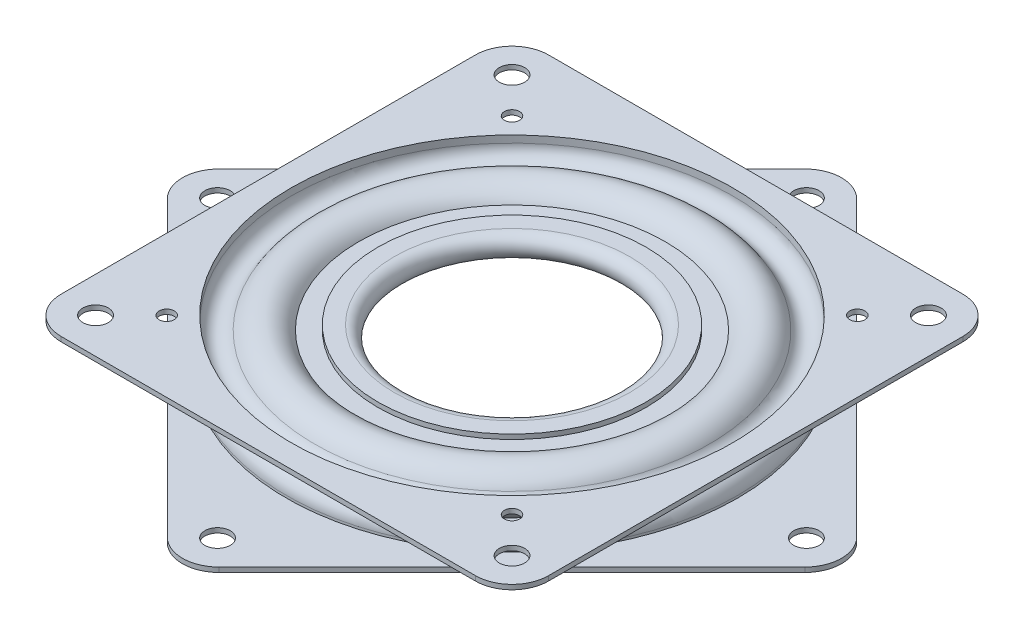
SolidWorks part; units mm, degrees
note: The reader was unsure of these and kept them because the rebuilt part matched: shared geometry of "Sketch3<3>".
material "Plain Carbon Steel"
ref_plane "Front Plane" through (0, 0, 0) normal (0, 0, 1) x (1, 0, 0)
ref_plane "Top Plane" through (0, 0, 0) normal (0, 1, 0) x (1, 0, 0)
ref_plane "Right Plane" through (0, 0, 0) normal (1, 0, 0) x (0, 0, -1)
sketch "Sketch1" plane through (0, 0, 0) normal (0, 1, 0) x (1, 0, 0)
  line L0 (0, -53.8815) -> (-53.8815, 0) construction
  line L1 (-38.1, 38.1) -> (38.1, 38.1) construction
  line L2 (-38.1, 38.1) -> (-38.1, -38.1) construction
  line L3 (-38.1, -38.1) -> (38.1, -38.1) construction
  line L4 (38.1, 38.1) -> (38.1, -38.1) construction
  line L5 (0, -38.1) -> (0, 38.1) construction
  line L6 (-38.1, 0) -> (38.1, 0) construction
  line L7 (0, -53.8815) -> (53.8815, 0) construction
  line L8 (-53.8815, 0) -> (0, 53.8815) construction
  line L9 (53.8815, 0) -> (0, 53.8815) construction
  line L10 (0, -53.8815) -> (0, 53.8815) construction
  line L11 (-53.8815, 0) -> (53.8815, 0) construction
  line L12 (38.1, -38.1) -> (-38.1, 38.1) construction
  line L13 (38.1, 38.1) -> (-38.1, -38.1) construction
  line L15 (-26.9875, 26.9875) -> (26.9875, 26.9875) construction
  line L16 (-26.9875, 26.9875) -> (-26.9875, -26.9875) construction
  line L17 (-26.9875, -26.9875) -> (26.9875, -26.9875) construction
  line L18 (26.9875, 26.9875) -> (26.9875, -26.9875) construction
  line L19 (-32.5437, 32.5437) -> (32.5437, 32.5437) construction
  line L20 (-32.5437, 32.5437) -> (-32.5437, -32.5437) construction
  line L21 (-32.5437, -32.5437) -> (32.5437, -32.5437) construction
  line L22 (32.5437, 32.5437) -> (32.5437, -32.5437) construction
  circle A0 centre (0, 0) radius 16.637 construction
  circle A1 centre (32.5437, -32.5437) radius 1.9844 construction
  circle A2 centre (-32.5437, -32.5437) radius 1.9844 construction
  circle A3 centre (-32.5437, 32.5437) radius 1.9844 construction
  circle A4 centre (32.5437, 32.5437) radius 1.9844 construction
  circle A5 centre (26.9875, 26.9875) radius 1.1906 construction
  circle A6 centre (-26.9875, 26.9875) radius 1.1906 construction
  circle A7 centre (-26.9875, -26.9875) radius 1.1906 construction
  circle A8 centre (26.9875, -26.9875) radius 1.1906 construction
  dimension "ID" = 33.274
  dimension "Inner Mounting Hole Dia." = 2.3813
  dimension "Outer Mounting Hole Dia." = 3.9688
  dimension "Length" = 76.2
  dimension "Width" = 76.2
  dimension "Inner Mounting Length" = 53.975
  dimension "Outer Mounting Length" = 65.0875
sketch "Sketch2" plane through (0, 0, 0) normal (0, 0, 1) x (1, 0, 0)
  line L0 (0, 3.937) -> (0, -3.937) construction
  line L1 (-38.1, 3.937) -> (38.1, 3.937) construction
  line L2 (-38.1, 3.937) -> (-38.1, -3.937) construction
  line L3 (-38.1, -3.937) -> (38.1, -3.937) construction
  line L4 (38.1, 3.937) -> (38.1, -3.937) construction
  line L5 (-38.1, 0) -> (38.1, 0) construction
  line L6 (-38.1, 3.2004) -> (38.1, 3.2004) construction
  line L7 (-38.1, -3.2004) -> (38.1, -3.2004) construction
  point P8 (0, 0)
  dimension "Overall Height" = 7.874
  dimension "Plate Thickness" = 0.7366
sketch "Sketch3" plane through (0, 0, 0) normal (0, 0, 1) x (1, 0, 0)
  line L0 (38.1, 3.937) -> (34.5177, 3.937)
  line L1 (-38.1, 3.937) -> (38.1, 3.937) construction
  line L2 (34.5177, 3.937) -> (34.5177, 2.8346)
  line L3 (23.943, 1.9406) -> (18.4086, 1.9406)
  line L4 (38.1, -3.937) -> (34.5177, -3.937)
  line L5 (-38.1, -3.937) -> (38.1, -3.937) construction
  line L6 (34.5177, -3.937) -> (34.5177, -2.8346)
  line L7 (34.5177, -2.8346) -> (34.5177, 2.8346) construction
  line L8 (23.528, -0.8661) -> (18.4086, -0.8661)
  line L9 (18.4086, 2.6772) -> (20.9683, 2.6772)
  line L10 (23.528, -0.8661) -> (34.5177, -0.8661) construction
  line L11 (16.637, 3.937) -> (16.637, -3.937) construction
  line L12 (16.637, 0) -> (-16.637, 0) construction
  line L13 (18.4086, 2.6772) -> (18.4086, 1.9406) construction
  line L14 (38.1, -3.937) -> (38.1, 3.937) construction
  line L15 (27.3685, 0) -> (38.1, 0) construction
  line L16 (27.3685, 0) -> (16.637, 0) construction
  line L17 (38.1, 3.937) -> (38.1, -3.937) construction
  line L18 (20.9683, -0.8661) -> (20.9683, 2.6772) construction
  line L19 (0, 3.937) -> (0, -3.937) construction
  arc A0 (34.5177, 2.8346) -> (30.8223, 1.8898) centre (32.5492, 2.8346) cw
  circle A1 centre (27.3685, 0) radius 3.937 construction
  arc A2 (30.8223, 1.8898) -> (23.943, 1.9406) centre (27.3685, 0) ccw
  arc A3 (34.5177, -2.8346) -> (30.8223, -1.8898) centre (32.5492, -2.8346) ccw
  arc A4 (30.8223, -1.8898) -> (23.528, -0.8661) centre (27.3685, 0) cw
  arc A5 (18.4086, -0.8661) -> (18.4086, 2.6772) centre (18.4086, 0.9055) cw
  point P26 (16.637, 0)
  point P38 (19.6885, 2.6772)
  dimension "D3" = 7.874
  dimension "D4" = 1.9685
  dimension "D1" = 0.7366
  dimension "D2" = 3.5433
  dimension "D5" = 6.6142
  dimension "D6" = 3.5823
revolve "Revolve-Thin1" add sketch "Sketch3" angle 360 about L0
revolve "Revolve-Thin2" add sketch "Sketch3<3>" angle 360 about L0
sketch "Sketch3<3>" plane through (0, 0, 0) normal (0, 0, 1) x (1, 0, 0) same geometry as "Sketch3"
sketch "Sketch4" plane through (0, 3.937, 0) normal (0, 1, 0) x (1, 0, 0)
  line L1 (-38.1, 38.1) -> (38.1, 38.1)
  line L2 (-38.1, 38.1) -> (-38.1, -38.1)
  line L3 (-38.1, -38.1) -> (38.1, -38.1)
  line L4 (38.1, 38.1) -> (38.1, -38.1)
  circle A0 centre (0, 0) radius 34.5177 construction
  circle A1 centre (0, 0) radius 34.5177
extrude "Boss-Extrude1" add sketch "Sketch4" against normal up to vertex (0.7366 mm away) up to point (38.1, 3.2004, 0)
sketch "Sketch5" plane through (0, -3.937, 0) normal (0, -1, 0) x (1, 0, 0)
  line L0 (-53.8815, 0) -> (0, 53.8815)
  line L1 (0, 53.8815) -> (53.8815, 0)
  line L2 (53.8815, 0) -> (0, -53.8815)
  line L3 (0, -53.8815) -> (-53.8815, 0)
  circle A0 centre (0, 0) radius 34.5177 construction
  circle A1 centre (0, 0) radius 34.5177
extrude "Boss-Extrude2" add sketch "Sketch5" against normal up to vertex (0.7366 mm away) up to point (-38.1, -3.2004, 0)
sketch "Sketch6" plane through (0, 0, 0) normal (0, 1, 0) x (1, 0, 0)
  circle A0 centre (-32.5437, 32.5437) radius 1.9844 construction
  circle A1 centre (-32.5437, -32.5437) radius 1.9844 construction
  circle A2 centre (32.5437, -32.5437) radius 1.9844 construction
  circle A3 centre (32.5437, 32.5437) radius 1.9844 construction
  circle A4 centre (-32.5437, 32.5437) radius 1.9844
  circle A5 centre (-32.5437, -32.5437) radius 1.9844
  circle A6 centre (32.5437, -32.5437) radius 1.9844
  circle A7 centre (32.5437, 32.5437) radius 1.9844
  circle A8 centre (26.9875, 26.9875) radius 1.1906 construction
  circle A9 centre (-26.9875, 26.9875) radius 1.1906 construction
  circle A10 centre (26.9875, -26.9875) radius 1.1906 construction
  circle A11 centre (-26.9875, -26.9875) radius 1.1906 construction
  circle A12 centre (26.9875, 26.9875) radius 1.1906
  circle A13 centre (-26.9875, 26.9875) radius 1.1906
  circle A14 centre (26.9875, -26.9875) radius 1.1906
  circle A15 centre (-26.9875, -26.9875) radius 1.1906
extrude "Cut-Extrude1" cut sketch "Sketch6" against normal through all both and the other way through all
sketch "Sketch7" plane through (0, 0, 0) normal (0, 1, 0) x (1, 0, 0)
  line L0 (-46.0238, 0) -> (0, 46.0238) construction
  line L1 (-46.0238, 0) -> (0, -46.0238) construction
  line L2 (0, 46.0238) -> (46.0238, 0) construction
  line L3 (0, -46.0238) -> (46.0238, 0) construction
  line L4 (-46.0238, 0) -> (46.0238, 0) construction
  line L5 (0, 46.0238) -> (0, -46.0238) construction
  line L6 (-53.8815, 0) -> (53.8815, 0) construction
  line L7 (0, -53.8815) -> (0, 53.8815) construction
  line L8 (-32.5437, -32.5437) -> (32.5437, -32.5437) construction
  circle A0 centre (46.0238, 0) radius 1.9844
  circle A1 centre (0, 46.0238) radius 1.9844
  circle A2 centre (-46.0238, 0) radius 1.9844
  circle A3 centre (0, -46.0238) radius 1.9844
  circle A4 centre (32.5437, -32.5437) radius 1.9844 construction
  circle A5 centre (32.5437, -32.5437) radius 1.9844 construction
  point P1 (0, 0)
extrude "Cut-Extrude2" cut sketch "Sketch7" against normal through all both and the other way through all
sketch "Sketch8" plane through (0, 0, 0) normal (0, 0, 1) x (1, 0, 0)
  line L0 (27.3685, 3.683) -> (27.3685, -3.683)
  arc A1 (27.3685, 3.683) -> (27.3685, -3.683) centre (27.3685, 0) cw
  circle A2 centre (27.3685, 0) radius 3.683
  circle A3 centre (27.3685, 0) radius 3.683 construction
  dimension "D1" = 0.254
revolve "Revolve1" add sketch "Sketch8" angle 360 about L0
pattern_circular "CirPattern1" count 22 over 360 about axis through (0, 0, 0) along (0, 1, 0) of bodies 110
fillet "Fillet1" radius 5.715 4 edges at (-38.1, 3.5687, -38.1) (38.1, 3.5687, -38.1) (-38.1, 3.5687, 38.1) (38.1, 3.5687, 38.1)
fillet "Fillet2" radius 5.715 4 edges at (-53.8815, -3.5687, 0) (0, -3.5687, -53.8815) (53.8815, -3.5687, 0) (0, -3.5687, 53.8815)
equation "\"D1@Sketch3\"=\"Plate Thickness@Sketch2\""
equation "\"D2@Sketch3\"=\"Overall Height@Sketch2\"*.45"
equation "\"D5@Sketch3\"=\"Overall Height@Sketch2\"*.84"
equation "\"D4@Sketch3\"=\"D3@Sketch3\"*.25"
equation "\"D3@Revolve-Thin2\"=\"Plate Thickness@Sketch2\""
equation "\"D3@Revolve-Thin1\"=\"Plate Thickness@Sketch2\""
equation "\"D1@Fillet2\"=\"D1@Fillet1\""
equation "\"D1@Fillet1\"=\"Length@Sketch1\"*.075"
